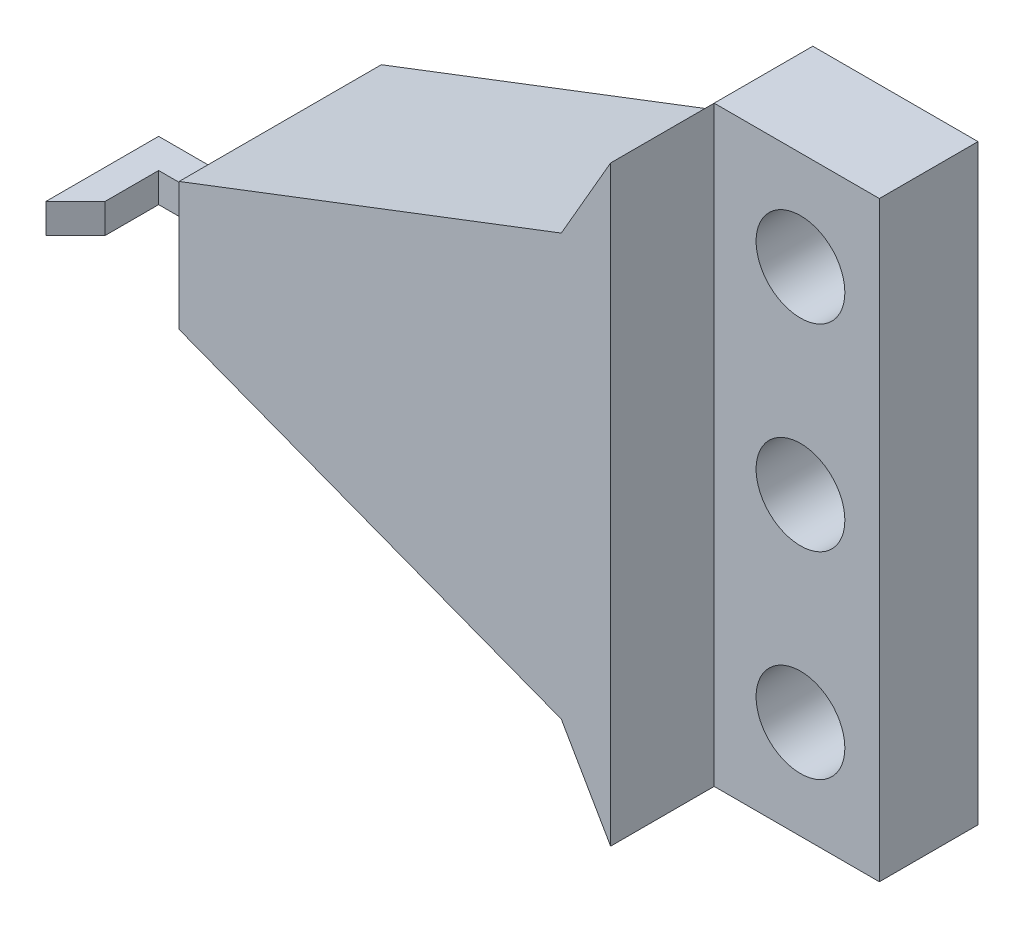
SolidWorks part; units mm, degrees
ref_plane "Front Plane" through (0, 0, 0) normal (0, 0, 1) x (1, 0, 0)
ref_plane "Top Plane" through (0, 0, 0) normal (0, 1, 0) x (1, 0, 0)
ref_plane "Right Plane" through (0, 0, 0) normal (1, 0, 0) x (0, 0, -1)
sketch "Sketch1" plane through (0, 0, 0) normal (0, 0, 1) x (1, 0, 0)
  line L0 (-4.064, -5.08) -> (-4.064, -15.24) construction
  line L1 (0, 0) -> (-8.509, 0)
  line L2 (0, 0) -> (0, -30.48)
  line L3 (0, -30.48) -> (-8.509, -30.48)
  line L4 (-30.734, -11.938) -> (-30.734, -18.542)
  line L5 (-4.064, -15.24) -> (-4.064, -25.4) construction
  line L6 (-30.734, -11.938) -> (-30.734, -18.542)
  line L7 (-30.734, -18.542) -> (-11.049, -26.0806)
  line L8 (-11.049, -26.0806) -> (-8.509, -30.48)
  line L9 (-30.734, -11.938) -> (-11.049, -4.3994)
  line L10 (-11.049, -4.3994) -> (-8.509, 0)
  line L11 (-8.509, 0) -> (-8.509, -30.48) construction
  line L12 (-8.509, 0) -> (-8.509, -30.48)
  line L14 (-35.814, -15.015) -> (-30.734, -15.015)
  line L15 (-35.814, -15.015) -> (-35.814, -15.465)
  line L16 (-35.814, -15.465) -> (-30.734, -15.465)
  line L17 (-30.734, -15.015) -> (-30.734, -15.465)
  circle A0 centre (-4.064, -5.08) radius 2.286
  circle A1 centre (-4.064, -25.4) radius 2.286
  circle A2 centre (-4.064, -15.24) radius 2.286
  point P1 (-30.734, -15.24)
  point P12 (0, -15.24)
  point P21 (-35.814, -15.24)
  dimension "D2" = 4.572
  dimension "D1" = 30.48
  dimension "D3" = 10.16
  dimension "D4" = 4.064
  dimension "D6" = 6.604
  dimension "D8" = 8.509
  dimension "D9" = 5.08
  dimension "D10" = 30
  dimension "D11" = 30
  dimension "D5" = 30.734
  dimension "D7" = 35.814
  dimension "D12" = 0.45
extrude "Boss-Extrude1" add sketch "Sketch1" along normal blind 5.08 contours L1 L12 L3 L2 A2 A1 A0 region at (-0.3165, -15.24, 0)
extrude "Boss-Extrude2" add sketch "Sketch1<3>" along normal blind 10.414 contours L12 L10 L9 L4 L7 L8 region at (-17.3291, -15.24, 0)
sketch "Sketch1<3>" plane through (0, 0, 0) normal (0, 0, 1) x (1, 0, 0) same geometry as "Sketch1"
ref_plane "Plane1" through (0, -15.24, 0) normal (0, -1, 0) x (-1, 0, 0)
sketch "Sketch2" plane through (0, -15.24, 0) normal (0, -1, 0) x (-1, 0, 0)
  line L0 (30.734, -6.39) -> (35.814, -6.39)
  line L1 (30.734, -10.414) -> (30.734, 0) construction
  line L2 (35.814, -6.39) -> (35.814, -12.192)
  line L3 (35.814, -12.192) -> (34.29, -12.192)
  line L4 (34.29, -12.192) -> (34.29, -7.914)
  line L5 (34.29, -7.914) -> (30.734, -7.914)
  line L6 (0, -5.08) -> (0, 0) construction
  line L7 (0, -5.08) -> (8.509, -5.08) construction
  line L8 (30.734, -6.39) -> (30.734, -7.914)
  line L9 (35.814, -12.192) -> (34.29, -10.668)
  dimension "D1" = 35.814
  dimension "D2" = 1.524
  dimension "D3" = 1.524
  dimension "D4" = 7.112
  dimension "D5" = 2.5
  dimension "D6" = 45
extrude "Boss-Extrude3" add sketch "Sketch2" along normal blind 0.762 and the other way blind 0.762 contours L9 L2 L0 L8 L5 L4 region at (-33.274, -15.24, 6.4671)
equation "\"D11@Sketch1\"=\"D10@Sketch1\""
